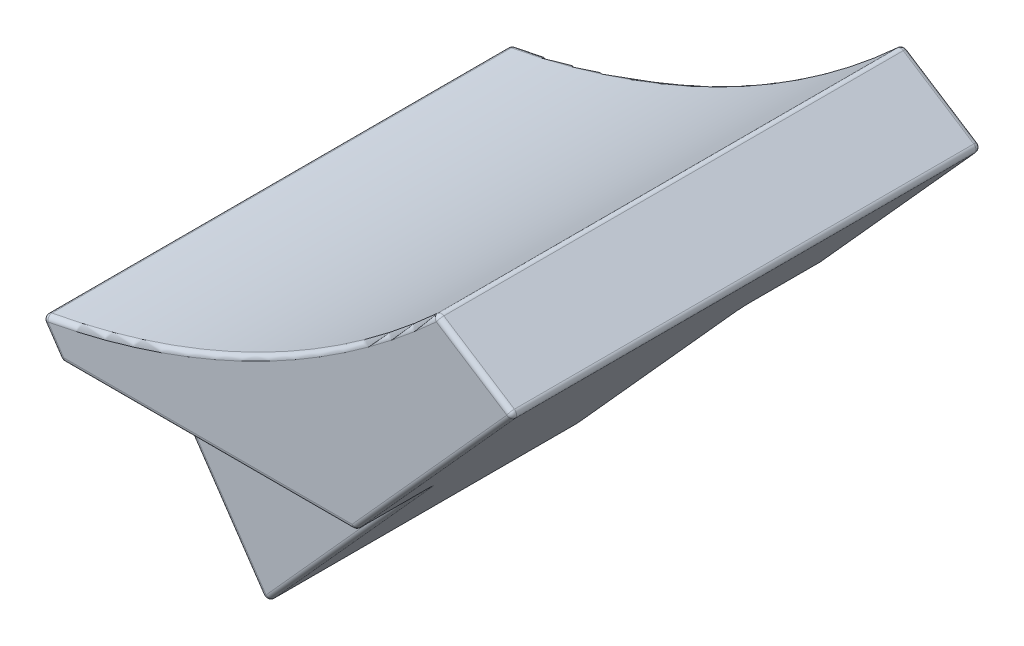
SolidWorks part; units mm, degrees
material "NEOPRENE"
ref_plane "Front Plane" through (0, 0, 0) normal (0, 0, 1) x (1, 0, 0)
ref_plane "Top Plane" through (0, 0, 0) normal (0, 1, 0) x (1, 0, 0)
ref_plane "Right Plane" through (0, 0, 0) normal (1, 0, 0) x (0, 0, -1)
sketch "Profile Sketch" plane through (0, 0, 0) normal (0, 0, 1) x (1, 0, 0)
  line L7 (0, 79.275) -> (0, -79.275) construction
  line L8 (27.2106, -29.3187) -> (31.2283, -31.9106)
  line L9 (31.2283, -31.9106) -> (14.5, -50.4892)
  line L10 (14.5, -50.4892) -> (6.9499, -39.3916)
  arc A8 (6.9499, -39.3916) -> (27.2106, -29.3187) centre (0, 0) ccw
  point P15 (0, 0)
  point P55 (14.5, -50.4892)
  point P58 (31.2283, -31.9106)
  dimension "D1" = 6.9499
  dimension "D9" = 40
  dimension "D4" = 13.4224
  dimension "D6" = 25
  dimension "D7" = 14.5
  dimension "D8" = 42
extrude "Body" add sketch "Profile Sketch" along normal mid plane 24
sketch "Front Cut Out Sketch" plane through (0, 0, 0) normal (0, 0, 1) x (1, 0, 0)
  line L0 (6.9499, -39.3916) -> (14.5, -50.4892) construction
  line L1 (8.0442, -41) -> (23.0441, -41)
  line L2 (8.0442, -41) -> (8.0442, -50.4892)
  line L3 (8.0442, -50.4892) -> (23.0441, -50.4892)
  line L4 (23.0441, -41) -> (23.0441, -50.4892)
  line L5 (8.0442, -41) -> (23.0441, -50.4892) construction
  line L6 (8.0442, -50.4892) -> (23.0441, -41) construction
  line L7 (14.5, -50.4892) -> (31.2283, -31.9106) construction
  point P0 (15.5441, -45.7446)
  dimension "D1" = 41
extrude "Front Cut Out" cut sketch "Front Cut Out Sketch" along normal through all from offset 8
mirror "Back Cut" about plane through (0, 0, 0) normal (0, 0, 1) of "Front Cut Out"
fillet "Fillet Edges" radius 0.25 24 edges at (15.5441, -41, 8) (15.5441, -41, -8) (15.5441, -41, -12) (15.5441, -41, 12) (18.7721, -45.7446, 8) (23.0441, -41, 10) (27.1362, -36.4553, 12) (27.1362, -36.4553, -12) (23.0441, -41, -10) (18.7721, -45.7446, -8) (31.2283, -31.9106, 0) (29.2194, -30.6146, 12) (29.2194, -30.6146, -12) (27.2106, -29.3187, 0) (17.8073, -35.8176, 12) (17.8073, -35.8176, -12) (6.9499, -39.3916, 0) (7.497, -40.1958, 12) (8.0442, -41, 10) (11.2721, -45.7446, 8) (14.5, -50.4892, 0) (11.2721, -45.7446, -8) (8.0442, -41, -10) (7.497, -40.1958, -12)
